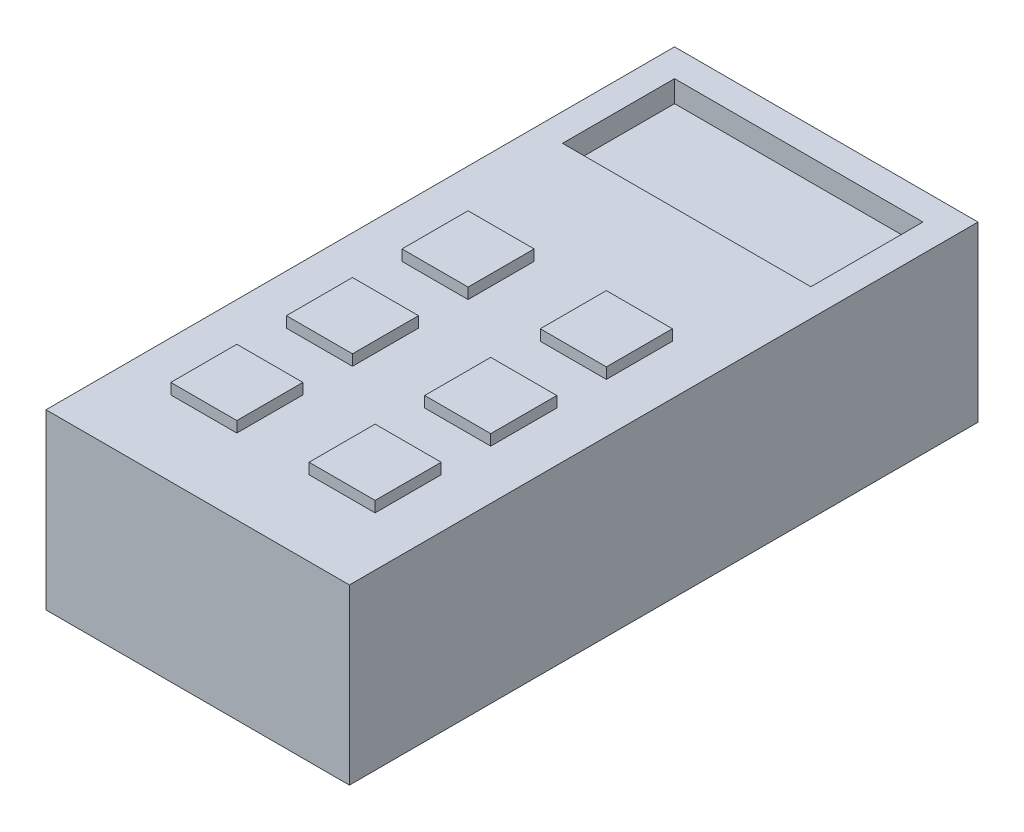
SolidWorks part; units mm, degrees
ref_plane "Front Plane" through (0, 0, 0) normal (0, 0, 1) x (1, 0, 0)
ref_plane "Top Plane" through (0, 0, 0) normal (0, 1, 0) x (1, 0, 0)
ref_plane "Right Plane" through (0, 0, 0) normal (1, 0, 0) x (0, 0, -1)
sketch "Sketch1" plane through (0, 0, 0) normal (0, 1, 0) x (1, 0, 0)
  line L1 (-35, -72.5) -> (35, -72.5)
  line L2 (-35, -72.5) -> (-35, 72.5)
  line L3 (-35, 72.5) -> (35, 72.5)
  line L4 (35, -72.5) -> (35, 72.5)
  line L5 (-35, -72.5) -> (35, 72.5) construction
  line L6 (-35, 72.5) -> (35, -72.5) construction
  point P0 (0, 0)
  dimension "D1" = 70
  dimension "D2" = 145
extrude "Boss-Extrude1" add sketch "Sketch1" along normal blind 40
sketch "Sketch2" plane through (0, 40, 0) normal (0, 1, 0) x (1, 0, 0)
  line L0 (-35, 72.5) -> (-35, -72.5) construction
  line L1 (-28.65, 66.15) -> (28.65, 66.15)
  line L2 (-28.65, 66.15) -> (-28.65, 40.3023)
  line L3 (-28.65, 40.3023) -> (28.65, 40.3023)
  line L4 (28.65, 66.15) -> (28.65, 40.3023)
  line L5 (35, -72.5) -> (35, 72.5) construction
  line L6 (35, 72.5) -> (-35, 72.5) construction
  dimension "D1" = 6.35
  dimension "D2" = 6.35
  dimension "D3" = 6.35
extrude "Cut-Extrude1" cut sketch "Sketch2" against normal blind 5
sketch "Sketch3" plane through (0, 40, 0) normal (0, 1, 0) x (1, 0, 0)
  line L0 (-35, 72.5) -> (-35, -72.5) construction
  line L1 (-23.57, 13.4341) -> (-8.33, 13.4341)
  line L2 (-23.57, 13.4341) -> (-23.57, -1.8059)
  line L3 (-23.57, -1.8059) -> (-8.33, -1.8059)
  line L4 (-8.33, 13.4341) -> (-8.33, -1.8059)
  line L5 (35, -72.5) -> (35, 72.5) construction
  line L6 (8.33, 13.4341) -> (23.57, 13.4341)
  line L7 (8.33, 13.4341) -> (8.33, -1.8059)
  line L8 (8.33, -1.8059) -> (23.57, -1.8059)
  line L9 (23.57, 13.4341) -> (23.57, -1.8059)
  dimension "D1" = 15.24
  dimension "D2" = 15.24
  dimension "D3" = 11.43
  dimension "D4" = 15.24
  dimension "D5" = 15.24
  dimension "D6" = 11.43
extrude "Boss-Extrude2" add sketch "Sketch3" along normal blind 2.5
pattern_linear "LPattern1" count 3 spacing 26.67 along (0, 0, 1) of "Boss-Extrude2"
